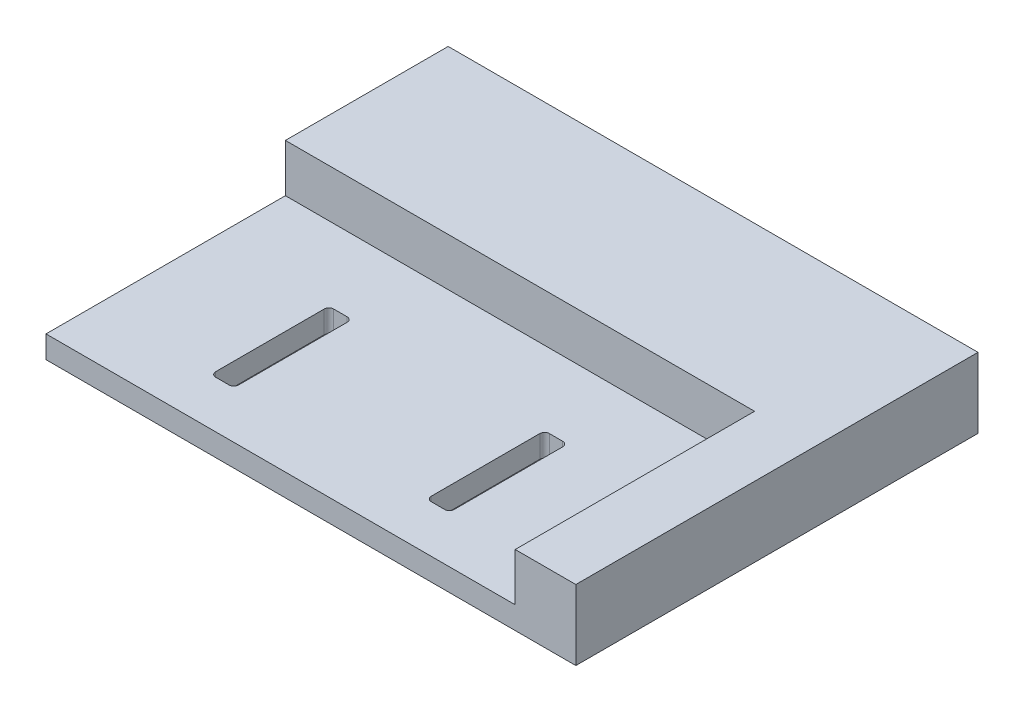
SolidWorks part; units mm, degrees
ref_plane "Front Plane" through (0, 0, 0) normal (0, 0, 1) x (1, 0, 0)
ref_plane "Top Plane" through (0, 0, 0) normal (0, 1, 0) x (1, 0, 0)
ref_plane "Right Plane" through (0, 0, 0) normal (1, 0, 0) x (0, 0, -1)
sketch "Sketch1" plane through (0, 0, 0) normal (0, 1, 0) x (1, 0, 0)
  line L1 (-83, 63) -> (83, 63)
  line L2 (-83, 63) -> (-83, -63)
  line L3 (-83, -63) -> (83, -63)
  line L4 (83, 63) -> (83, -63)
  dimension "D1" = 166
  dimension "D2" = 126
  dimension "D3" = 83
  dimension "D4" = 63
extrude "Boss-Extrude1" add sketch "Sketch1" along normal blind 7
sketch "Sketch2" plane through (0, 7, 0) normal (0, 1, 0) x (1, 0, 0)
  line L0 (-83, 63) -> (-83, 12)
  line L1 (-83, 63) -> (-83, -63) construction
  line L2 (-83, 12) -> (64, 12)
  line L3 (64, 12) -> (64, -63)
  line L4 (-83, -63) -> (83, -63) construction
  line L5 (64, -63) -> (83, -63)
  line L6 (83, -63) -> (83, 63) construction
  line L7 (83, -63) -> (83, 63)
  line L8 (83, 63) -> (-83, 63)
  dimension "D1" = 51
  dimension "D2" = 19
extrude "Boss-Extrude2" add sketch "Sketch2" along normal blind 15
sketch "Sketch3" plane through (0, 7, 0) normal (0, 1, 0) x (1, 0, 0)
  line L0 (-83, 12) -> (64, 12) construction
  line L1 (-44.67, -11.18) -> (-40.47, -11.18)
  line L2 (-46.17, -12.68) -> (-46.17, -46.68)
  line L3 (-44.67, -48.18) -> (-40.47, -48.18)
  line L4 (-38.97, -12.68) -> (-38.97, -46.68)
  line L5 (22.89, -11.19) -> (27.09, -11.19)
  line L6 (21.39, -12.69) -> (21.39, -46.69)
  line L7 (22.89, -48.19) -> (27.09, -48.19)
  line L8 (28.59, -12.69) -> (28.59, -46.69)
  line L10 (64, 12) -> (64, -63) construction
  arc A0 (27.09, -48.19) -> (28.59, -46.69) centre (27.09, -46.69) ccw
  arc A1 (28.59, -12.69) -> (27.09, -11.19) centre (27.09, -12.69) ccw
  arc A2 (22.89, -11.19) -> (21.39, -12.69) centre (22.89, -12.69) ccw
  arc A3 (22.89, -48.19) -> (21.39, -46.69) centre (22.89, -46.69) cw
  arc A4 (-44.67, -48.18) -> (-46.17, -46.68) centre (-44.67, -46.68) cw
  arc A5 (-40.47, -48.18) -> (-38.97, -46.68) centre (-40.47, -46.68) ccw
  arc A6 (-38.97, -12.68) -> (-40.47, -11.18) centre (-40.47, -12.68) ccw
  arc A7 (-46.17, -12.68) -> (-44.67, -11.18) centre (-44.67, -12.68) cw
  point P18 (-46.17, -48.18)
  point P25 (-46.17, -11.18)
  dimension "D3" = 1.5
  dimension "D1" = 37
  dimension "D2" = 7.2
  dimension "D4" = 67.56
  dimension "D5" = 23.18
  dimension "D6" = 23.19
  dimension "D7" = 102.97
extrude "Cut-Extrude1" cut sketch "Sketch3" against normal up to next
